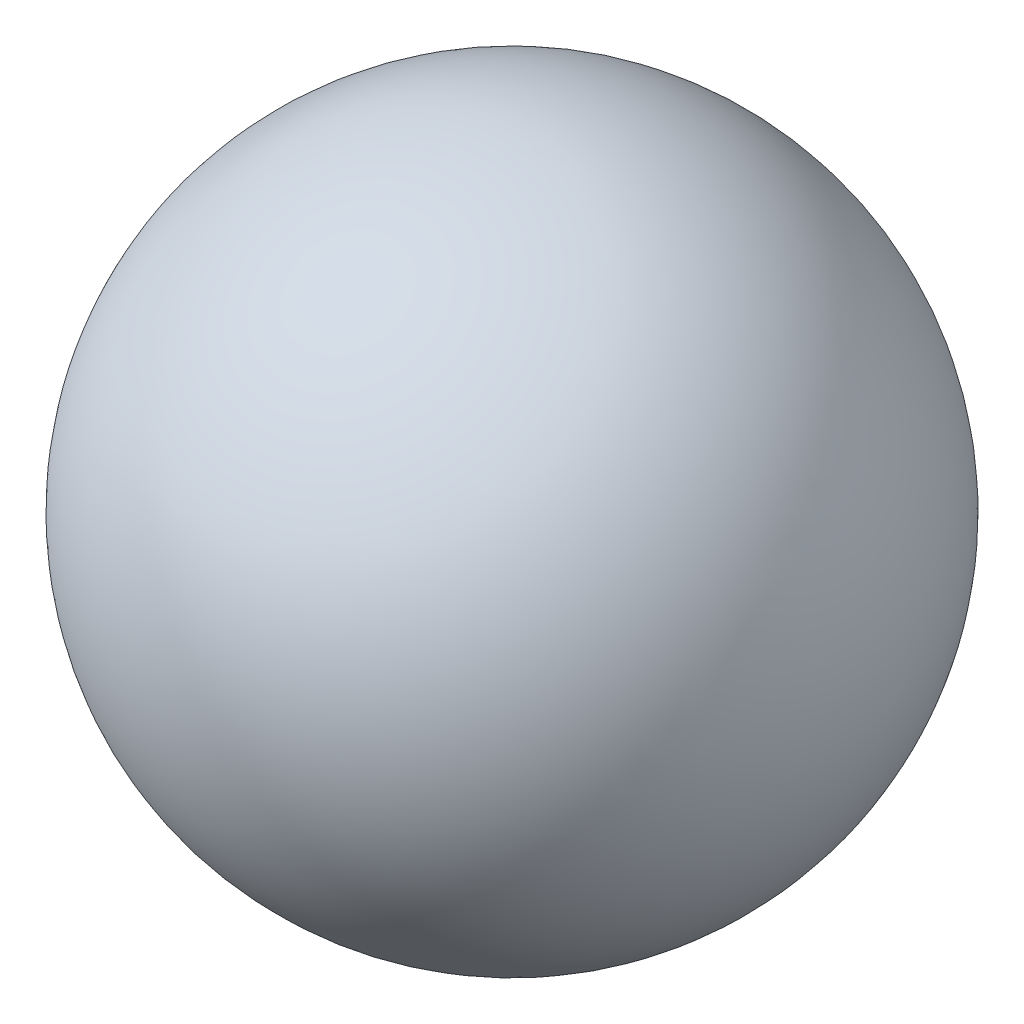
SolidWorks part; units mm, degrees
ref_plane "Front Plane" through (0, 0, 0) normal (0, 0, 1) x (1, 0, 0)
ref_plane "Top Plane" through (0, 0, 0) normal (0, 1, 0) x (1, 0, 0)
ref_plane "Right Plane" through (0, 0, 0) normal (1, 0, 0) x (0, 0, -1)
sketch "Sketch1" plane through (0, 0, 0) normal (0, 1, 0) x (1, 0, 0)
  line L0 (-39.5075, 15.2674) -> (20.4925, 15.2674)
  arc A1 (20.4925, 15.2674) -> (-39.5075, 15.2674) centre (-9.5075, 15.2674) ccw
revolve "Revolve3" add sketch "Sketch1" angle 360 about L0 region at (-9.5075, 0, -27.9998)
ref_point "center"
ref_axis "Axis1" through (-9.5075, 0, -15.2674) along (0, 1, 0)
ref_plane "Plane1" through (0, 30, 0) normal (0, 1, 0) x (1, 0, 0)
ref_plane "Plane2" through (0, -30, 0) normal (0, -1, 0) x (-1, 0, 0)
ref_point "wrist up"
ref_point "wrist down"
ref_axis "wrsit_up+right" through (-9.5075, 30, -15.2674) along (1, 0, 0)
ref_axis "wrsit_up+front" through (-9.5075, 30, -15.2674) along (0, 0, 1)
ref_axis "wrsit_dwon+right" through (-9.5075, -30, -15.2674) along (1, 0, 0)
ref_axis "wrsit_dwon+front" through (-9.5075, -30, -15.2674) along (0, 0, 1)
ref_axis "tilt_ax" through (-9.5075, 0, -15.2674) along (0, 0, 1)
ref_axis "flex_ax" through (-9.5075, 0, -15.2674) along (1, 0, 0)
